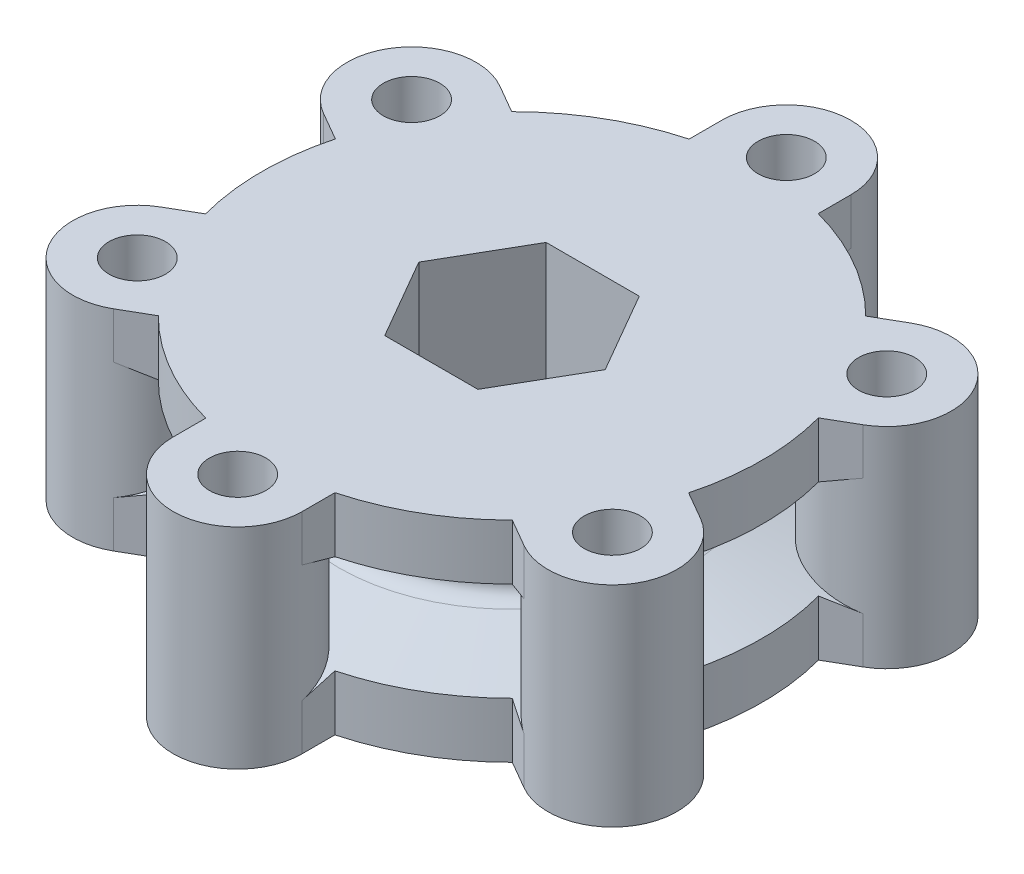
SolidWorks part; units mm, degrees
material "PLA/ABS"
ref_plane "Front Plane" through (0, 0, 0) normal (0, 0, 1) x (1, 0, 0)
ref_plane "Top Plane" through (0, 0, 0) normal (0, 1, 0) x (1, 0, 0)
ref_plane "Right Plane" through (0, 0, 0) normal (1, 0, 0) x (0, 0, -1)
other "Bounding Box"
ref_plane "Default Plane" through (13.8565, 3.175, 6.7999) normal (0, -1, 0) x (-1, 0, 0)
sketch "Sketch1" plane through (0, 0, 0) normal (0, 1, 0) x (1, 0, 0)
  line L0 (22.4506, -22.4506) -> (0, 0) construction
  line L1 (0, 0) -> (22.4506, 22.4506) construction
  line L2 (0, 0) -> (0, 31.75) construction
  circle A0 centre (0, 0) radius 31.75
  point P3 (0, 31.75)
  point P4 (31.75, 0)
  point P5 (-31.75, 0)
  point P6 (0, -31.75)
  point P7 (22.4506, 22.4506)
  point P8 (22.4506, -22.4506)
  dimension "D1" = 63.5
  dimension "D2" = 45
extrude "Boss-Extrude1" add sketch "Sketch1" along normal mid plane 16.51
ref_plane "Plane2" through (-31.75, 0, 0) normal (-1, 0, 0) x (0, 0, 1)
sketch "Sketch9" plane through (-31.75, 0, 0) normal (-1, 0, 0) x (0, 0, 1)
  line L0 (-0.635, -8.255) -> (0.635, -8.255)
  line L1 (-31.75, -8.255) -> (31.75, -8.255) construction
  line L2 (0.635, -8.255) -> (0.635, 0)
  line L3 (31.75, 8.255) -> (-31.75, 8.255) construction
  line L5 (-0.635, 0) -> (-0.635, -8.255)
  line L6 (0.635, -8.255) -> (0, -8.255) construction
  line L7 (0, -8.255) -> (0, 8.255) construction
  line L9 (-0.635, 0) -> (0.635, 0) construction
  line L10 (0.635, 0) -> (0.635, 8.255)
  line L11 (0.635, 8.255) -> (-0.635, 8.255)
  line L13 (-0.635, 8.255) -> (-0.635, 0)
  point P14 (0, 0)
  dimension "D2" = 1.27
extrude "Cut-Extrude4" cut sketch "Sketch9" against normal blind 0.635
sketch "Sketch4" plane through (0, 0, 0) normal (0, 0, 1) x (1, 0, 0)
  line L0 (-31.75, -8.255) -> (-29.21, -8.255)
  line L1 (-31.7436, -8.255) -> (31.75, -8.255) construction
  line L4 (31.75, 8.255) -> (-31.7436, 8.255) construction
  line L5 (-29.21, 8.255) -> (-31.75, 8.255)
  line L6 (-31.75, 8.255) -> (-31.75, -8.255)
  line L7 (-6.35, 0) -> (0, 0) construction
  line L8 (-29.21, -8.255) -> (-29.21, -6.6675)
  line L9 (-29.21, -6.6675) -> (-6.35, 0)
  line L10 (-6.35, 0) -> (-29.21, 6.6675)
  line L11 (-29.21, 6.6675) -> (-29.21, 8.255)
  point P17 (-31.75, 0)
  dimension "D1" = 2.54
  dimension "D2" = 25.4
  dimension "D3" = 1.5875
pattern_circular "CirPattern2" count 20 over 360 about axis through (0, -8.255, 0) along (0, 1, 0) of "Cut-Extrude4"
ref_axis "Axis1" through (0, -9.0805, 0) along (0, 1, 0)
sketch "Sketch3" plane through (0, 8.255, 0) normal (0, 1, 0) x (1, 0, 0)
  line L0 (0, 0) -> (0, 21.59) construction
  line L1 (0, 21.59) -> (0, 31.75) construction
  circle A0 centre (0, 21.59) radius 2.2225
  circle A1 centre (0, 0) radius 31.75 construction
  circle A2 centre (0, 21.59) radius 5.08
  dimension "D2" = 4.445
  dimension "D3" = 10.16
  dimension "D1" = 10.16
move or copy body "Body-Move/Copy1" [suppressed] parameters "D1"=0, "D2"=0, "D3"=0
revolve "Cut-Revolve2" cut sketch "Sketch4" angle 360 about axis through (0, -9.0805, 0) along (0, 1, 0)
sketch "Sketch5" plane through (0, 8.255, 0) normal (0, 1, 0) x (1, 0, 0)
  circle A0 centre (0, 21.59) radius 5.08
  circle A1 centre (0, 21.59) radius 2.2225 construction
  circle A3 centre (0, 21.59) radius 2.2225
  circle A4 centre (0, 21.59) radius 5.08 construction
extrude "Boss-Extrude2" add sketch "Sketch5" against normal through all
sketch "Sketch12" plane through (0, 8.255, 0) normal (0, 1, 0) x (1, 0, 0)
  line L0 (-18.6975, 10.795) -> (0, 0) construction
  line L1 (-18.6975, -10.795) -> (-18.6975, 10.795) construction
  line L2 (-18.6975, 10.795) -> (0, 21.59) construction
  line L3 (-18.6975, -10.795) -> (0, 0) construction
  line L4 (0, 0) -> (0, 21.59) construction
  circle A0 centre (-18.6975, 10.795) radius 5.08
  circle A1 centre (0, 21.59) radius 5.08 construction
  dimension "D3" = 120
extrude "Boss-Extrude6" add sketch "Sketch12" against normal through all
sketch "Sketch17" plane through (0, 0, 0) normal (0, 1, 0) x (1, 0, 0)
  line L0 (0, 21.59) -> (0, 0) construction
  line L1 (0, 0) -> (-18.6975, 10.795) construction
  line L2 (0, 0) -> (-18.6975, -10.795) construction
  line L3 (-23.0969, -13.335) -> (-25.2966, -14.605)
  line L4 (0, 26.67) -> (0, 29.21)
  line L5 (-21.2375, -6.3956) -> (-19.0103, -5.1097)
  line L6 (-19.0103, 5.1097) -> (-21.2375, 6.3956)
  line L7 (-16.1575, 15.1944) -> (-13.9303, 13.9085)
  line L8 (-5.08, 21.59) -> (-5.08, 19.0182)
  circle A0 centre (0, 21.59) radius 5.08 construction
  circle A1 centre (-18.6975, 10.795) radius 5.08 construction
  arc A2 (0, 26.67) -> (-5.08, 21.59) centre (0, 21.59) ccw
  arc A3 (-16.1575, 15.1944) -> (-21.2375, 6.3956) centre (-18.6975, 10.795) ccw
  arc A5 (-5.08, 19.0182) -> (-13.9303, 13.9085) centre (0, 0) ccw
  circle A6 centre (0, 21.59) radius 2.2225 construction
  arc A7 (-21.2375, -6.3956) -> (-23.0969, -13.335) centre (-18.6975, -10.795) ccw
  circle A8 centre (0, 0) radius 29.21 construction
  circle A9 centre (0, 21.59) radius 2.2225
  circle A10 centre (0, 0) radius 29.21 construction
  arc A11 (0, 29.21) -> (-25.2966, -14.605) centre (0, 0) ccw
  arc A12 (-19.0103, 5.1097) -> (-19.0103, -5.1097) centre (0, 0) ccw
  circle A13 centre (-18.6975, 10.795) radius 2.2225
  circle A15 centre (-18.6975, -10.795) radius 2.2225
  dimension "D1" = 9.525
extrude "Cut-Extrude5" cut sketch "Sketch17" against normal through all both and the other way through all
pattern_circular "CirPattern1" count 3 over 360 about axis through (0, 6.6675, 0) along (0, -1, 0) of "Boss-Extrude2", "Boss-Extrude6", "Cut-Extrude5"
sketch "Sketch18" plane through (0, -8.255, 0) normal (0, -1, 0) x (1, 0, 0)
  circle A0 centre (0, 0) radius 19.685 construction
  circle A1 centre (0, 0) radius 12.7
  arc A2 (-5.08, 19.0182) -> (-13.9303, 13.9085) centre (0, 0) ccw construction
  circle A3 centre (0, 0) radius 6.35 construction
  circle A4 centre (0, 0) radius 6.35 construction
  dimension "D1" = 25.4
extrude "Boss-Extrude9" add sketch "Sketch18" against normal through all
fillet "Fillet5" radius 1.27 2 edges at (0, -1.8521, -12.7) (0, 1.8521, 12.7)
sketch "Sketch24" plane through (0, -8.255, 0) normal (0, -1, 0) x (1, 0, 0)
  line L1 (3.6662, -6.35) -> (7.3323, 0)
  line L2 (7.3323, 0) -> (3.6662, 6.35)
  line L3 (3.6662, 6.35) -> (-3.6662, 6.35)
  line L4 (-3.6662, 6.35) -> (-7.3323, 0)
  line L5 (-7.3323, 0) -> (-3.6662, -6.35)
  line L6 (-3.6662, -6.35) -> (3.6662, -6.35)
  circle A0 centre (0, 0) radius 4 construction
  circle A1 centre (0, 0) radius 6.35 construction
  dimension "D1" = 8
  dimension "D2" = 12.7
extrude "Cut-Extrude7" cut sketch "Sketch24" against normal through all
combine bodies "Combine3" [suppressed] bodies to combine 116 189
delete or keep bodies "Body-Delete/Keep 4" [suppressed] type keep bodies bodies 117
sketch "Sketch7" [suppressed] plane through (0, -8.255, 0) normal (0, -1, 0) x (1, 0, 0)
  circle A0 centre (0, 0) radius 44.45
  circle A1 centre (0, 0) radius 38.1 construction
  dimension "D1" = 6.35
extrude "Boss-Extrude4" [suppressed] add sketch "Sketch7" against normal offset from surface (19.685 mm away) 3.175 separate body up to face at (0, 8.255, 0) offset beyond the face yes
combine bodies "Combine2" [suppressed] operation type add bodies to combine 110 114
sketch "Sketch15" [suppressed] plane through (0, 0, 0) normal (1, 0, 0) x (0, 0, -1)
  line L0 (-38.1, -8.255) -> (-43.18, -13.335)
  line L1 (-43.18, -13.335) -> (-36.83, -13.335)
  line L2 (-36.83, -13.335) -> (-31.75, -8.255)
  line L3 (-31.75, -8.255) -> (-38.1, -8.255)
  dimension "D1" = 5.08
  dimension "D2" = 45
  dimension "D3" = 6.35
ref_axis "Axis2" [suppressed] through (0, -9.0805, 0) along (0, 1, 0)
revolve "Revolve1" [suppressed] add sketch "Sketch15" angle 360 about axis through (0, -9.0805, 0) along (0, 1, 0)
fillet "Fillet4" [suppressed] radius 6.35
sketch "Sketch27" [suppressed] plane through (0, 11.43, 0) normal (0, 1, 0) x (1, 0, 0)
  line L0 (37.5671, 6.35) -> (44.45, 6.35)
  line L1 (44.45, -6.35) -> (37.5671, -6.35)
  line L2 (38.1, 0) -> (44.45, 0) construction
  circle A0 centre (44.45, 0) radius 1.905
  arc A1 (37.5671, -6.35) -> (37.5671, 6.35) centre (0, 0) ccw
  circle A2 centre (0, 0) radius 38.1 construction
  arc A3 (44.45, 6.35) -> (44.45, -6.35) centre (44.45, 0) cw
  dimension "D2" = 3.81
  dimension "D3" = 6.35
  dimension "D1" = 6.35
extrude "Boss-Extrude13" [suppressed] add sketch "Sketch27" against normal blind 9.525
pattern_circular "CirPattern7" [suppressed] count 3 over 360 of bodies 177
split "Split1" [suppressed] bodies to split 124
sketch "Sketch19" [suppressed] plane through (0, 11.43, 0) normal (0, 1, 0) x (1, 0, 0)
  line L0 (-20.447, 35.4152) -> (-19.177, 33.2155)
  line L1 (-20.447, -35.4152) -> (-19.177, -33.2155)
  line L2 (-40.894, 0) -> (0, 0) construction
  arc A0 (-19.177, 33.2155) -> (-19.177, -33.2155) centre (0, 0) ccw
  circle A1 centre (0, 0) radius 38.1 construction
  arc A2 (-20.447, 35.4152) -> (-20.447, -35.4152) centre (0, 0) ccw
  dimension "D2" = 2.54
  dimension "D3" = 0.254
  dimension "D1" = 120
extrude "Boss-Extrude10" [suppressed] add sketch "Sketch19" against normal blind 6.35 separate body
sketch "Sketch21" [suppressed] plane through (0, 11.43, 0) normal (0, 1, 0) x (1, 0, 0)
  line L0 (-19.177, 33.2155) -> (-19.05, 32.9956)
  line L1 (-19.177, -33.2155) -> (-19.05, -32.9956)
  line L2 (-19.177, 33.2155) -> (-20.447, 35.4152) construction
  line L3 (-20.447, -35.4152) -> (-19.177, -33.2155) construction
  arc A1 (-19.177, 33.2155) -> (-19.177, -33.2155) centre (0, 0) ccw construction
  arc A2 (-19.05, 32.9956) -> (-19.05, -32.9956) centre (0, 0) ccw
  arc A3 (-19.177, 33.2155) -> (-19.177, -33.2155) centre (0, 0) ccw
  circle A4 centre (0, 0) radius 38.1 construction
extrude "Boss-Extrude11" [suppressed] add sketch "Sketch21" against normal blind 3.1496
pattern_circular "CirPattern6" [suppressed] count 3 over 360 reverse direction yes of bodies 137 132
combine bodies "Combine4" [suppressed] bodies to combine 137 137 135 134
chamfer "Chamfer4" [suppressed] distance 0.635 angle 45
delete or keep bodies "Body-Delete/Keep 1" [suppressed] type delete bodies bodies 133
delete or keep bodies "Body-Delete/Keep 2" [suppressed] type delete bodies bodies 121
mirror "Mirror1" [suppressed] about plane through (0, 0, 0) normal (1, 0, 0) of bodies 121
delete or keep bodies "Body-Delete/Keep 3" [suppressed] type delete bodies bodies 121
sketch "Sketch28" [suppressed] plane through (0, 8.255, 0) normal (0, -1, 0) x (1, 0, 0)
  circle A0 centre (0, 0) radius 15.24
  dimension "D1" = 30.48
extrude "Boss-Extrude14" [suppressed] add sketch "Sketch28" along normal blind 0.635
sketch "Sketch29" [suppressed] plane through (0, 7.62, 0) normal (0, -1, 0) x (1, 0, 0)
  circle A0 centre (0, 0) radius 9.144
  dimension "D1" = 18.288
extrude "Boss-Extrude15" [suppressed] add sketch "Sketch29" along normal blind 10.16
sketch "Sketch30" [suppressed] plane through (0, -8.255, 0) normal (0, -1, 0) x (1, 0, 0)
  circle A12 centre (0, 0) radius 30.48
  circle A13 centre (0, 0) radius 27.94
  circle A14 centre (0, 0) radius 31.75 construction
  dimension "D1" = 1.27
  dimension "D2" = 2.54
extrude "Boss-Extrude16" [suppressed] add sketch "Sketch30" along normal blind 1.6002 separate body
sketch "Sketch31" [suppressed] plane through (0, -9.8552, 0) normal (0, -1, 0) x (1, 0, 0)
  line L0 (-5.9055, 21.59) -> (-5.9055, 29.9024)
  line L1 (-5.9055, 29.9024) -> (5.9055, 29.9024)
  line L2 (5.9055, 29.9024) -> (5.9055, 21.59)
  circle A1 centre (0, 21.59) radius 2.7305
  arc A2 (5.9055, 21.59) -> (-5.9055, 21.59) centre (0, 21.59) cw
  circle A3 centre (0, 21.59) radius 2.2225 construction
  circle A4 centre (0, 0) radius 30.48 construction
  dimension "D1" = 3.175
  dimension "D2" = 5.461
extrude "Boss-Extrude17" [suppressed] add sketch "Sketch31" against normal up to surface (1.6002 mm away) up to face at (0, -8.255, 0)
fillet "Fillet6" [suppressed] radius 2.54
pattern_circular "CirPattern8" [suppressed] count 6 over 360 of bodies 182
sketch "Sketch32" [suppressed] plane through (0, -9.8552, 0) normal (0, -1, 0) x (1, 0, 0)
  line L0 (0, 0) -> (-2.3034, 32.9396) construction
  line L1 (2.3034, 32.9396) -> (0.3104, 30.4784)
  line L2 (0, 0) -> (0, 33.02) construction
  line L3 (-1.8597, 30.4232) -> (-2.3034, 32.9396)
  line L4 (-2.3034, 32.9396) -> (-0.3104, 30.4784)
  line L5 (-0.3104, 30.4784) -> (-1.8597, 30.4232)
  line L6 (1.8597, 30.4232) -> (2.3034, 32.9396)
  line L7 (0.3104, 30.4784) -> (1.8597, 30.4232)
  circle A0 centre (0, 0) radius 30.48 construction
  circle A1 centre (0, 0) radius 33.02 construction
  circle A2 centre (0, 0) radius 31.75 construction
  dimension "D2" = 1.27
  dimension "D1" = 6
  dimension "D3" = 35
  dimension "D4" = 4
extrude "Boss-Extrude18" [suppressed] add sketch "Sketch32" against normal up to surface (1.6002 mm away) up to face at (0, -8.255, 0)
fillet "Fillet7" [suppressed] radius 0.635
pattern_circular "CirPattern9" [suppressed] count 10 over 360 of bodies 184
delete or keep bodies "Body-Delete/Keep 5" [suppressed] bodies 185
